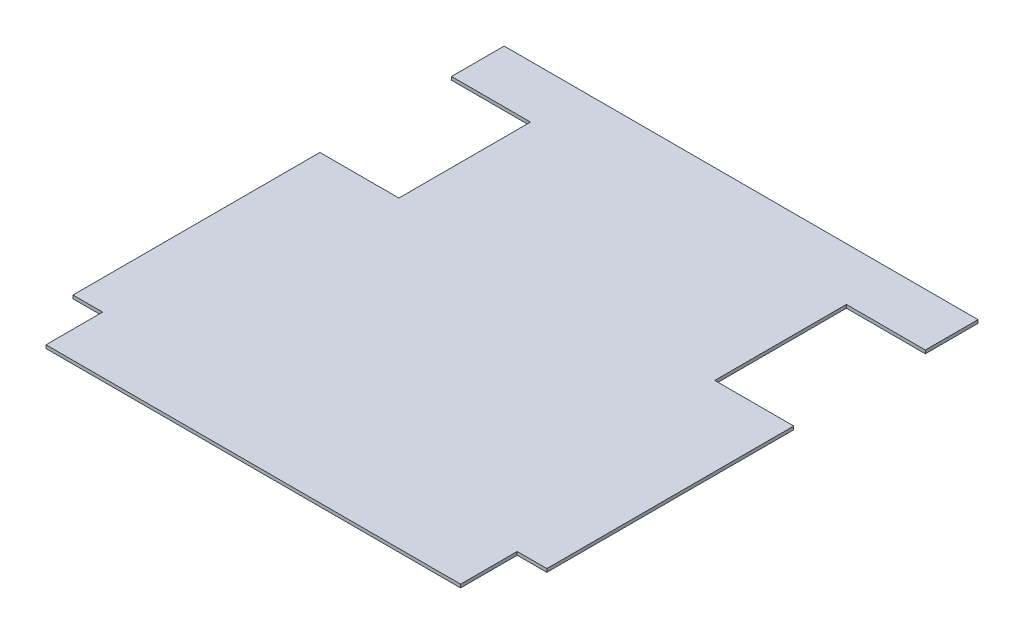
SolidWorks part; units mm, degrees
material "Acrylic (Medium-high impact)"
ref_plane "Front Plane" through (0, 0, 0) normal (0, 0, 1) x (1, 0, 0)
ref_plane "Top Plane" through (0, 0, 0) normal (0, 1, 0) x (1, 0, 0)
ref_plane "Right Plane" through (0, 0, 0) normal (1, 0, 0) x (0, 0, -1)
sketch "Sketch1" plane through (0, 0, 0) normal (0, 1, 0) x (1, 0, 0)
  line L0 (381, 238.252) -> (457.2, 238.252)
  line L1 (0, 0) -> (28.575, 0)
  line L2 (0, 0) -> (0, 238.252)
  line L3 (0, 238.252) -> (76.2, 238.252)
  line L4 (457.2, 0) -> (457.2, 238.252)
  line L5 (381, 365.252) -> (457.2, 365.252)
  line L6 (76.2, 238.252) -> (76.2, 365.252)
  line L7 (428.625, 0) -> (457.2, 0)
  line L8 (381, 238.252) -> (381, 365.252)
  line L9 (0, 365.252) -> (76.2, 365.252)
  line L10 (0, 365.252) -> (0, 416.052)
  line L11 (0, 416.052) -> (457.2, 416.052)
  line L12 (457.2, 365.252) -> (457.2, 416.052)
  line L14 (28.575, 0) -> (28.575, -54.61)
  line L15 (28.575, -54.61) -> (428.625, -54.61)
  line L16 (428.625, 0) -> (428.625, -54.61)
  dimension "D1" = 457.2
  dimension "D2" = 238.252
  dimension "D3" = 28.575
  dimension "D4" = 76.2
  dimension "D5" = 76.2
  dimension "D6" = 50.8
  dimension "D7" = 177.8
  dimension "D8" = 76.2
  dimension "D9" = 76.2
  dimension "D10" = 28.575
  dimension "D11" = 54.61
extrude "Boss-Extrude1" add sketch "Sketch1" along normal blind 3.175
